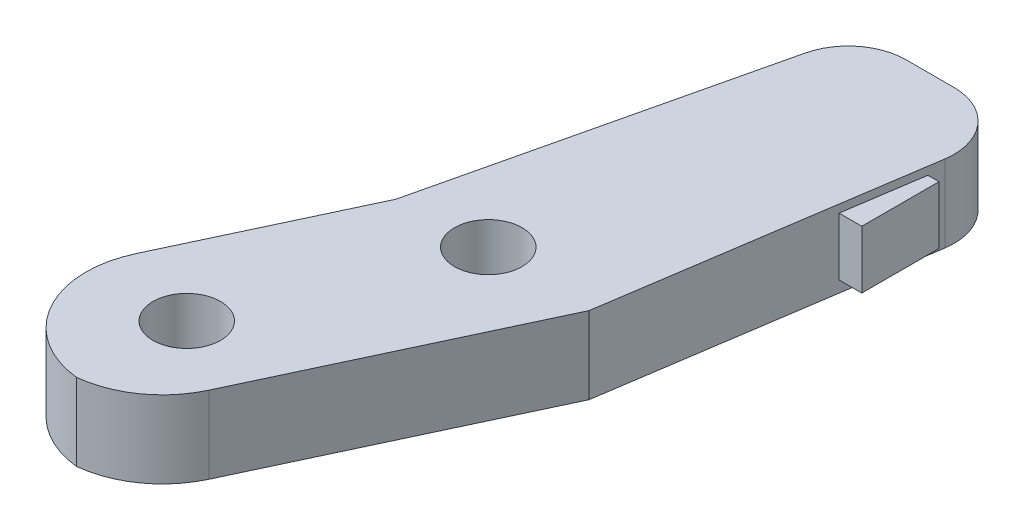
SolidWorks part; units mm, degrees
ref_plane "Front Plane" through (0, 0, 0) normal (0, 0, 1) x (1, 0, 0)
ref_plane "Top Plane" through (0, 0, 0) normal (0, 1, 0) x (1, 0, 0)
ref_plane "Right Plane" through (0, 0, 0) normal (1, 0, 0) x (0, 0, -1)
sketch "Sketch1" plane through (0, 0, 0) normal (0, 1, 0) x (1, 0, 0)
  line L0 (0, 0) -> (7.6273, 16.3041)
  line L1 (7.6273, 16.3041) -> (12.2143, 35.771)
  line L6 (17.6273, 16.3041) -> (10, 0)
  line L7 (10, 0) -> (0, 0)
  line L9 (17.6273, 16.3041) -> (20.5598, 35.771)
  line L10 (20.5598, 35.771) -> (12.2143, 35.771)
  dimension "D1" = 10
  dimension "D2" = 18
  dimension "D3" = 18
  dimension "D4" = 20
extrude "Boss-Extrude1" add sketch "Sketch1" along normal blind 4
fillet "Fillet1" radius 5 2 edges at (10, 2, 0) (0, 2, 0)
fillet "Fillet2" radius 3 2 edges at (12.2143, 2, -35.771) (20.5598, 2, -35.771)
sketch "Sketch2" plane through (0, 4, 0) normal (0, 1, 0) x (1, 0, 0)
  circle A0 centre (7.6677, 5.4139) radius 1.75
  circle A1 centre (12.17, 16.5373) radius 1.75
  dimension "D1" = 3.5
  dimension "D2" = 3.5
  dimension "D3" = 12
extrude "Cut-Extrude1" cut sketch "Sketch2" against normal through all
ref_plane "Plane1" through (20.5, 0, 0) normal (1, 0, 0) x (0, 0, -1)
sketch "Sketch4" plane through (20.5, 0, 0) normal (1, 0, 0) x (0, 0, -1)
  line L1 (31.5611, 3.5919) -> (27.5611, 3.5919)
  line L2 (31.5611, 3.5919) -> (31.5611, 0.5919)
  line L3 (31.5611, 0.5919) -> (27.5611, 0.5919)
  line L4 (27.5611, 3.5919) -> (27.5611, 0.5919)
  dimension "D1" = 3
  dimension "D2" = 4
extrude "Boss-Extrude2" add sketch "Sketch4" against normal up to surface (0.5744 mm away) up to face at (18.8339, 2, -24.3141)
